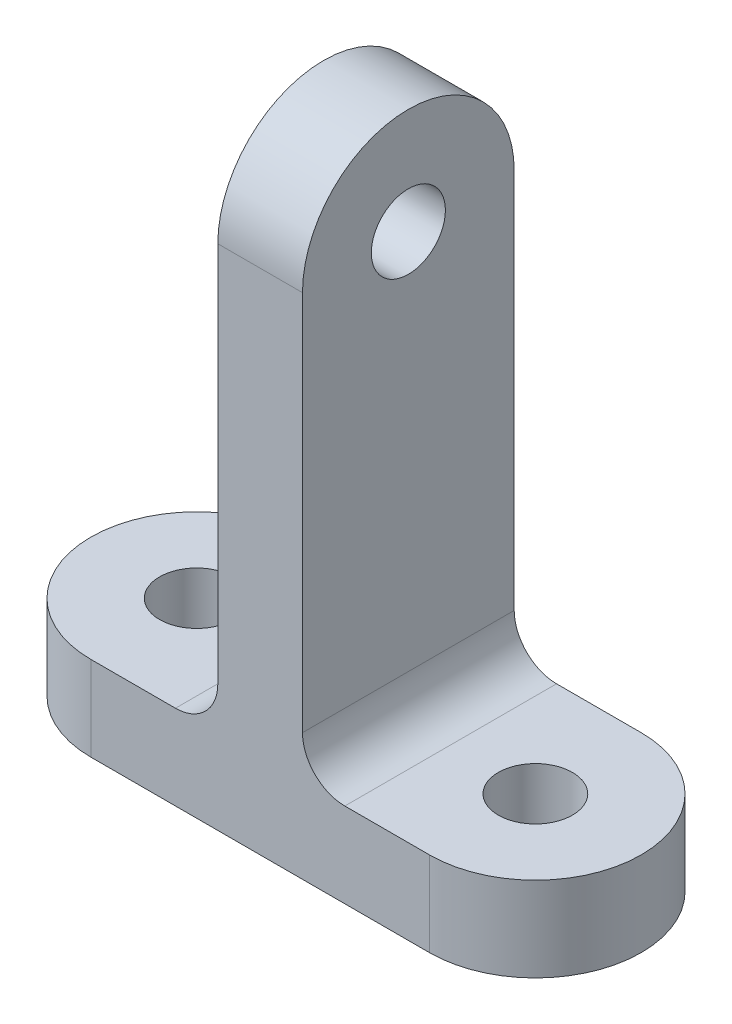
SolidWorks part; units mm, degrees
ref_plane "Front Plane" through (0, 0, 0) normal (0, 0, 1) x (1, 0, 0)
ref_plane "Top Plane" through (0, 0, 0) normal (0, 1, 0) x (1, 0, 0)
ref_plane "Right Plane" through (0, 0, 0) normal (1, 0, 0) x (0, 0, -1)
sketch "Sketch1" plane through (0, 0, 0) normal (0, 1, 0) x (1, 0, 0)
  line L0 (-8, 5) -> (8, 5)
  line L1 (8, -5) -> (-8, -5)
  circle A0 centre (-8, 0) radius 1.75
  circle A1 centre (8, 0) radius 1.75
  circle A2 centre (-8, 0) radius 5
  circle A3 centre (8, 0) radius 5
  dimension "D1" = 3.5
  dimension "D2" = 3.5
  dimension "D5" = 10
  dimension "D6" = 10
  dimension "D3" = 8
  dimension "D4" = 8
extrude "Boss-Extrude1" add sketch "Sketch1" along normal blind 4 contours A2 A0 | A3 L0 A2 L1 | A3 A1 region at (0, 0, 0) region at (-4.5645, 0, -3.4355) region at (11.4355, 0, -3.4355)
sketch "Sketch2" plane through (0, 4, 0) normal (0, 1, 0) x (1, 0, 0)
  line L0 (8, -5) -> (-8, -5) construction
  line L1 (2, 5) -> (-2, 5)
  line L2 (2, 5) -> (2, -5)
  line L3 (2, -5) -> (-2, -5)
  line L4 (-2, 5) -> (-2, -5)
  line L5 (2, 5) -> (-2, -5) construction
  line L6 (2, -5) -> (-2, 5) construction
  point P0 (0, 0)
  dimension "D1" = 4
extrude "Boss-Extrude2" add sketch "Sketch2" along normal blind 25
sketch "Sketch3" plane through (2, 0, 0) normal (1, 0, 0) x (0, 0, -1)
  line L0 (-5, 29) -> (5, 29) construction
  line L5 (-5, 4) -> (5, 4)
  line L6 (5, 4) -> (5, 29)
  line L7 (5, 29) -> (-5, 29)
  line L8 (-5, 29) -> (-5, 4)
  line L9 (-5, 4) -> (5, 4)
  line L10 (5, 4) -> (5, 29)
  line L11 (5, 29) -> (-5, 29)
  line L12 (-5, 29) -> (-5, 4)
  circle A0 centre (0, 24) radius 1.75
  circle A1 centre (0, 24) radius 5
  line M9 (5, 29) -> (-5, 29)
  line M10 (-5, 29) -> (-5, 4)
  dimension "D2" = 3.5
  dimension "D1" = 5
  dimension "D3" = 0
extrude "Cut-Extrude1" cut sketch "Sketch3" against normal up to surface (4 mm away) contours A1 L11 M10 | A1 L10 M9 | A0 region at (2, 27.8832, 3.8832) region at (2, 27.8832, -3.8832) region at (2, 24, 0) up to face at (-2, 16.5, 0)
fillet "Fillet1" radius 2 1 edges at (2, 4, 0)
fillet "Fillet2" radius 2 1 edges at (-2, 4, 0)
